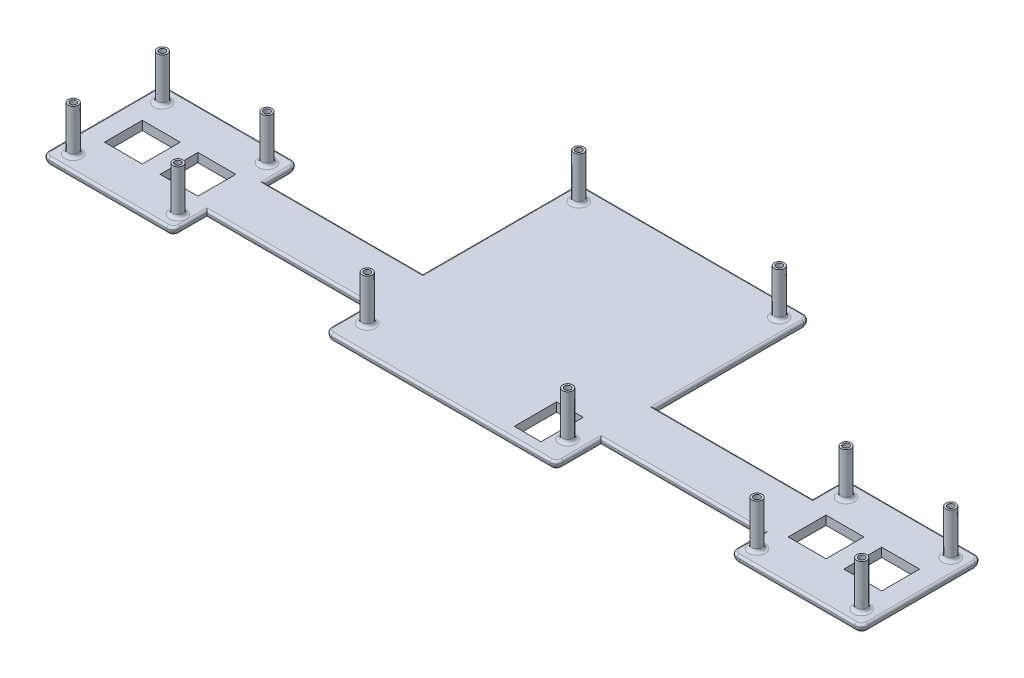
SolidWorks part; units mm, degrees
ref_plane "Front Plane" through (0, 0, 0) normal (0, 0, 1) x (1, 0, 0)
ref_plane "Top Plane" through (0, 0, 0) normal (0, 1, 0) x (1, 0, 0)
ref_plane "Right Plane" through (0, 0, 0) normal (1, 0, 0) x (0, 0, -1)
sketch "Sketch1" plane through (0, 0, 0) normal (0, 1, 0) x (1, 0, 0)
  line L0 (0, 0) -> (0, 114) construction
  line L1 (0, 0) -> (52, 0)
  line L2 (52, 0) -> (52, 20)
  line L3 (52, 20) -> (125, 20)
  line L4 (125, 20) -> (125, 5)
  line L5 (125, 5) -> (184, 5)
  line L6 (184, 5) -> (184, 59)
  line L7 (184, 59) -> (123, 59)
  line L8 (123, 59) -> (123, 44)
  line L9 (123, 44) -> (52, 44)
  line L10 (52, 44) -> (52, 114)
  line L11 (52, 114) -> (0, 114)
  line L12 (0, 114) -> (0, 0)
  dimension "D1" = 52
  dimension "D2" = 70
  dimension "D3" = 24
  dimension "D4" = 20
  dimension "D5" = 15
  dimension "D6" = 15
  dimension "D7" = 61
  dimension "D8" = 73
  dimension "D9" = 71
  dimension "D10" = 54
extrude "Boss-Extrude1" add sketch "Sketch1" along normal blind 4
mirror "Mirror3" about plane through (0, 4, -114) normal (1, 0, 0) of "Boss-Extrude1"
sketch "Sketch11" plane through (0, 4, 0) normal (0, 1, 0) x (1, 0, 0)
  line L0 (52, 44) -> (52, 114) construction
  line L1 (52, 114) -> (-52, 114) construction
  line L4 (123, 59) -> (123, 44) construction
  line L6 (184, 59) -> (123, 59) construction
  line L7 (125, 5) -> (184, 5) construction
  line L8 (184, 5) -> (184, 59) construction
  line L9 (-184, 5) -> (-184, 59) construction
  line L11 (-123, 59) -> (-123, 44) construction
  line L14 (-52, 0) -> (-52, 20) construction
  circle A0 centre (-45, 107) radius 2.25
  circle A1 centre (45, 107) radius 2.25
  circle A2 centre (-45, 12) radius 2.25
  circle A3 centre (45, 12) radius 2.25
  circle A4 centre (-130, 52) radius 2.25
  circle A5 centre (-177, 52) radius 2.25
  circle A6 centre (-177, 12) radius 2.25
  circle A7 centre (-130, 12) radius 2.25
  circle A8 centre (130, 52) radius 2.25
  circle A10 centre (177, 52) radius 2.25
  circle A11 centre (177, 12) radius 2.25
  circle A12 centre (130, 12) radius 2.25
  point P0 (-45, 107)
  point P1 (45, 107)
  point P2 (45, 12)
  point P3 (-45, 12)
  point P4 (130, 52)
  point P5 (130, 12)
  point P6 (177, 12)
  point P7 (177, 52)
  point P8 (-130, 52)
  point P9 (-130, 12)
  point P10 (-177, 52)
  point P11 (-177, 12)
  dimension "D14" = 4.5
  dimension "D1" = 7
  dimension "D2" = 7
  dimension "D3" = 95
  dimension "D4" = 7
  dimension "D5" = 7
  dimension "D6" = 7
  dimension "D7" = 7
  dimension "D8" = 7
  dimension "D9" = 7
  dimension "D10" = 7
  dimension "D11" = 90
  dimension "D12" = 47
  dimension "D13" = 40
sketch "Sketch13" plane through (0, 4, 0) normal (0, 1, 0) x (1, 0, 0)
  line L0 (-52, 0) -> (52, 0) construction
  line L1 (28, 24) -> (40, 24)
  line L2 (28, 24) -> (28, 5)
  line L3 (28, 5) -> (40, 5)
  line L4 (40, 24) -> (40, 5)
  line L5 (28, 24) -> (40, 5) construction
  line L6 (28, 5) -> (40, 24) construction
  line L7 (52, 44) -> (52, 114) construction
  point P0 (34, 14.5)
  dimension "D1" = 19
  dimension "D2" = 12
  dimension "D3" = 5
  dimension "D4" = 12
extrude "Cut-Extrude1" cut sketch "Sketch13" against normal through all
extrude "Boss-Extrude2" add sketch "Sketch11" along normal blind 20
sketch "Sketch14" plane through (0, 24, 0) normal (0, 1, 0) x (1, 0, 0)
  circle A0 centre (-177, 52) radius 1.4
  circle A1 centre (-130, 52) radius 1.4
  circle A2 centre (-177, 12) radius 1.4
  circle A3 centre (-130, 12) radius 1.4
  circle A4 centre (-45, 107) radius 1.4
  circle A5 centre (45, 107) radius 1.4
  circle A6 centre (-45, 12) radius 1.4
  circle A7 centre (45, 12) radius 1.4
  circle A8 centre (130, 52) radius 1.4
  circle A9 centre (130, 12) radius 1.4
  circle A10 centre (177, 52) radius 1.4
  circle A11 centre (177, 12) radius 1.4
  dimension "D1" = 2.8
extrude "Cut-Extrude2" cut sketch "Sketch14" against normal blind 12
sketch "Sketch15" plane through (0, 4, 0) normal (0, 1, 0) x (1, 0, 0)
  line L9 (132.5, 40.5) -> (149.5, 40.5)
  line L10 (132.5, 40.5) -> (132.5, 23.5)
  line L11 (132.5, 23.5) -> (149.5, 23.5)
  line L12 (149.5, 40.5) -> (149.5, 23.5)
  line L13 (157.5, 40.5) -> (174.5, 40.5)
  line L14 (157.5, 40.5) -> (157.5, 23.5)
  line L15 (157.5, 23.5) -> (174.5, 23.5)
  line L16 (174.5, 40.5) -> (174.5, 23.5)
  line L23 (-174.5, 40.5) -> (-157.5, 40.5)
  line L24 (-174.5, 40.5) -> (-174.5, 23.5)
  line L25 (-174.5, 23.5) -> (-157.5, 23.5)
  line L26 (-157.5, 40.5) -> (-157.5, 23.5)
  line L27 (-149.5, 40.5) -> (-132.5, 40.5)
  line L28 (-149.5, 40.5) -> (-149.5, 23.5)
  line L29 (-149.5, 23.5) -> (-132.5, 23.5)
  line L30 (-132.5, 40.5) -> (-132.5, 23.5)
  dimension "D7" = 17
  dimension "D8" = 17
  dimension "D12" = 17
  dimension "D13" = 17
  dimension "D20" = 17
  dimension "D21" = 17
  dimension "D22" = 17
  dimension "D23" = 17
extrude "Cut-Extrude3" cut sketch "Sketch15" against normal through all
fillet "Fillet3" radius 3 20 edges at (52, 0, -10) (88.5, 0, -20) (125, 0, -12.5) (154.5, 0, -5) (184, 0, -32) (153.5, 0, -59) (123, 0, -51.5) (87.5, 0, -44) (52, 0, -79) (0, 0, -114) (-52, 0, -79) (-87.5, 0, -44) (-123, 0, -51.5) (-153.5, 0, -59) (-184, 0, -32) (-154.5, 0, -5) (-125, 0, -12.5) (-88.5, 0, -20) (-52, 0, -10) (0, 0, 0)
fillet "Fillet5" radius 1 20 edges at (184, 4, -32) (154.5, 4, -5) (125, 4, -12.5) (153.5, 4, -59) (123, 4, -51.5) (87.5, 4, -44) (88.5, 4, -20) (52, 4, -10) (0, 4, 0) (-52, 4, -10) (52, 4, -79) (0, 4, -114) (-52, 4, -79) (-87.5, 4, -44) (-123, 4, -51.5) (-125, 4, -12.5) (-88.5, 4, -20) (-154.5, 4, -5) (-153.5, 4, -59) (-184, 4, -32)
fillet "Fillet6" radius 3 24 edges at (51.1213, 0.8787, -113.1213) (-51.1213, 0.8787, -113.1213) (-123.8787, 0.8787, -58.1213) (-183.1213, 0.8787, -58.1213) (-183.1213, 0.8787, -5.8787) (-125.8787, 0.8787, -5.8787) (-51.1213, 0.8787, -0.8787) (51.1213, 0.8787, -0.8787) (123.8787, 0.8787, -58.1213) (125.8787, 0.8787, -5.8787) (183.1213, 0.8787, -5.8787) (183.1213, 0.8787, -58.1213) (183.7071, 3.7071, -58.7071) (183.7071, 3.7071, -5.2929) (125.2929, 3.7071, -5.2929) (123.2929, 3.7071, -58.7071) (51.7071, 3.7071, -0.2929) (-51.7071, 3.7071, -0.2929) (-125.2929, 3.7071, -5.2929) (-183.7071, 3.7071, -5.2929) (-183.7071, 3.7071, -58.7071) (-123.2929, 3.7071, -58.7071) (-51.7071, 3.7071, -113.7071) (51.7071, 3.7071, -113.7071)
fillet "Fillet7" radius 1.5 12 edges at (-130, 4, -9.75) (-177, 4, -9.75) (-177, 4, -49.75) (-130, 4, -49.75) (130, 4, -49.75) (177, 4, -49.75) (177, 4, -9.75) (130, 4, -9.75) (-45, 4, -9.75) (45, 4, -9.75) (-45, 4, -104.75) (45, 4, -104.75)
sketch "Sketch18" plane through (0, 0, 0) normal (0, -1, 0) x (1, 0, 0)
  line L0 (34.3641, -85.6775) -> (-39.3952, -85.6775) construction
  text T0 "Techno Beasts" font "Century Gothic" height in points 25
extrude "Boss-Extrude3" add sketch "Sketch18" along normal blind 0.5
